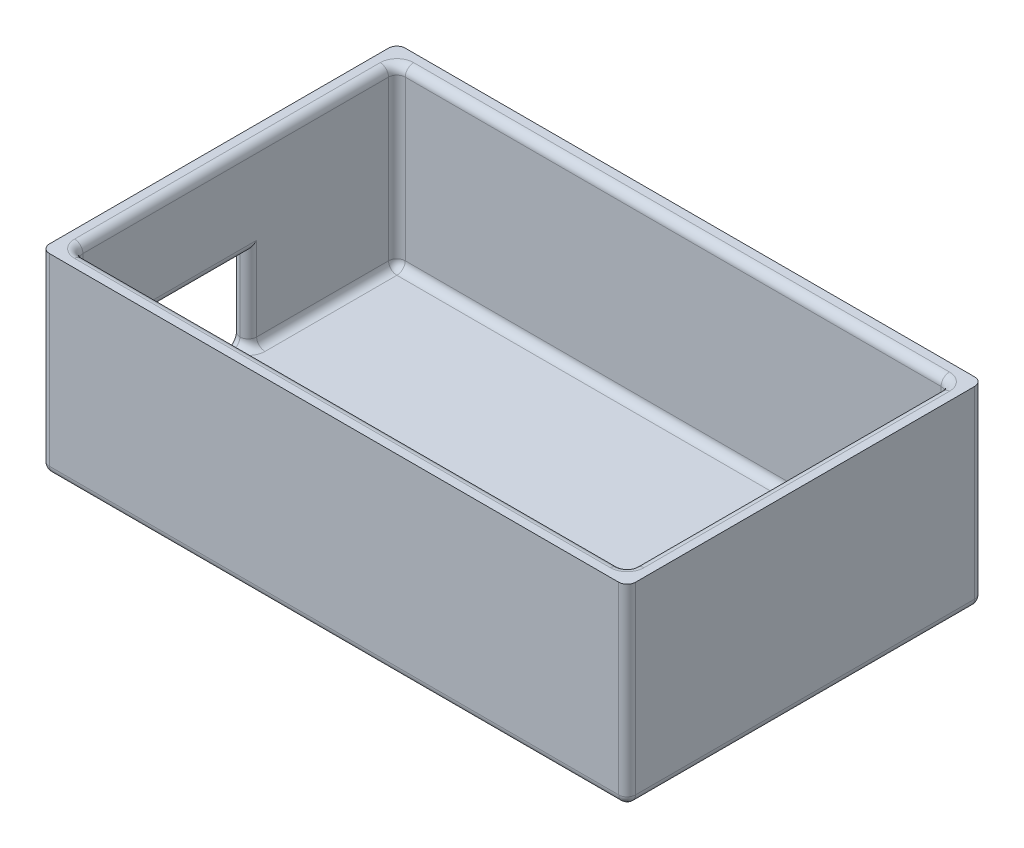
SolidWorks part; units mm, degrees
ref_plane "Front Plane" through (0, 0, 0) normal (0, 0, 1) x (1, 0, 0)
ref_plane "Top Plane" through (0, 0, 0) normal (0, 1, 0) x (1, 0, 0)
ref_plane "Right Plane" through (0, 0, 0) normal (1, 0, 0) x (0, 0, -1)
sketch "Sketch1" plane through (0, 0, 0) normal (0, 1, 0) x (1, 0, 0)
  line L0 (-7.25, 9.25) -> (25.25, 9.25) construction
  line L1 (-32.25, 4.75) -> (17.75, 4.75) construction
  line L2 (-32.25, 4.75) -> (-32.25, -14.25) construction
  line L3 (-32.25, -14.25) -> (17.75, -14.25) construction
  line L4 (17.75, 4.75) -> (17.75, -14.25) construction
  line L9 (25.25, 9.25) -> (25.25, -18.75) construction
  line L18 (25.25, -18.75) -> (32.25, -18.75) construction
  line L19 (32.25, -18.75) -> (32.25, 18.75) construction
  line L20 (32.25, 18.75) -> (-7.25, 18.75) construction
  line L21 (-7.25, 18.75) -> (-7.25, 9.25) construction
  line L22 (17.75, -4.75) -> (25.25, -4.75) construction
  line L23 (-34.25, -20.75) -> (34.25, -20.75) construction
  line L24 (-34.25, -20.75) -> (-34.25, 20.75) construction
  line L25 (-34.25, 20.75) -> (34.25, 20.75) construction
  line L26 (34.25, -20.75) -> (34.25, 20.75) construction
  line L27 (-35, -21.25) -> (35, 21.25) construction
  line L28 (-34.25, 20.75) -> (34.25, -20.75) construction
  line L29 (-35, -21.25) -> (35, -21.25)
  line L30 (-35, -21.25) -> (-35, 21.25)
  line L31 (-35, 21.25) -> (35, 21.25)
  line L32 (35, -21.25) -> (35, 21.25)
  point P20 (-54.0448, -32.3593)
  point P21 (0, 0)
  point P22 (-35.1885, -21.5843)
  dimension "D1" = 19
  dimension "D2" = 50
  dimension "D3" = 39.5
  dimension "D4" = 9.5
  dimension "D5" = 37.5
  dimension "D6" = 7
  dimension "D7" = 7.5
  dimension "D8" = 2
  dimension "D9" = 2
  dimension "D10" = 2
  dimension "D11" = 2
  dimension "D12" = 70
  dimension "D13" = 42.5
extrude "Boss-Extrude1" add sketch "Sketch1" against normal blind 2
sketch "Sketch2" plane through (0, 0, 0) normal (0, 1, 0) x (-1, 0, 0)
  line L0 (33, -19.25) -> (-33, 19.25) construction
  line L1 (33, 19.25) -> (-33, 19.25)
  line L2 (33, 19.25) -> (33, -19.25)
  line L3 (33, -19.25) -> (-33, -19.25)
  line L4 (-33, 19.25) -> (-33, -19.25)
  line L5 (35, 21.25) -> (-35, 21.25)
  line L6 (35, 21.25) -> (35, -21.25)
  line L7 (35, -21.25) -> (-35, -21.25)
  line L8 (-35, 21.25) -> (-35, -21.25)
  line L9 (35, 21.25) -> (-35, -21.25) construction
  line L10 (32.25, 4.75) -> (35, 4.75) construction
  line L11 (33, 11) -> (35, 11)
  line L12 (33, 11) -> (33, -1.5)
  line L13 (33, -1.5) -> (35, -1.5)
  line L14 (35, 11) -> (35, -1.5)
  line L15 (-35, 21.25) -> (-35, -21.25) construction
  line L16 (32.25, -4.75) -> (32.25, 14.25) construction
  line L17 (-35, -21.25) -> (35, -21.25) construction
  point P4 (-37, -19.25)
  point P5 (-37, -19.25)
  point P10 (0, 0)
  point P15 (-37, 23.6538)
  point P21 (-35, -21.25)
  point P27 (35, 21.25)
  line M26 (35, -21.25) -> (35, 21.25)
  line M27 (35, 21.25) -> (-35, 21.25)
  line M28 (-35, 21.25) -> (-35, -21.25)
  line M29 (-35, -21.25) -> (35, -21.25)
  dimension "D1" = 2
  dimension "D2" = 2
  dimension "D3" = 12.5
extrude "Boss-Extrude2" add sketch "Sketch2" along normal blind 21 contours L13 L2 L3 L4 L1 L11 L6 M27 M28 M29 M26
fillet "Fillet1" [suppressed] radius 1
sketch "Sketch3" plane through (0, 21, 0) normal (0, 1, 0) x (1, 0, 0)
  line L1 (-35, 1.5) -> (-33, 1.5)
  line L2 (-35, 1.5) -> (-35, -11)
  line L3 (-35, -11) -> (-33, -11)
  line L4 (-33, 1.5) -> (-33, -11)
extrude "Boss-Extrude3" add sketch "Sketch3" against normal offset from surface (11 mm away) 10 up to face at (-17, 0, 2.375)
fillet "Fillet2" radius 1 28 edges at (0, 0, -19.25) (33, 0, 0) (0, 0, 19.25) (-33, 0, 15.125) (-33, 0, -10.375) (35, 9.5, -21.25) (-35, 9.5, -21.25) (-35, 0, 4.75) (-35, 5, 11) (-35, 10, 4.75) (-35, 5, -1.5) (-35, 9.5, 21.25) (35, 9.5, 21.25) (0, -2, 21.25) (35, -2, 0) (0, -2, -21.25) (-35, -2, 0) (33, 10.5, 19.25) (33, 10.5, -19.25) (-33, 10.5, 19.25) (-33, 5, 11) (-33, 5, -1.5) (-33, 10, 4.75) (-33, 10.5, -19.25) (0, 21, -19.25) (33, 21, 0) (0, 21, 19.25) (-33, 21, 0)
